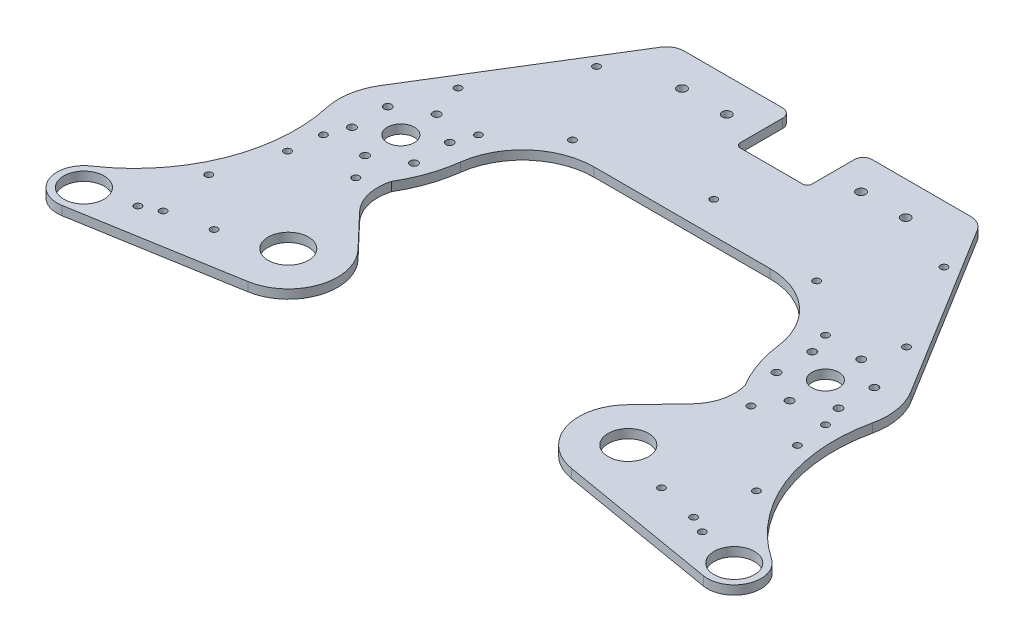
SolidWorks part; units mm, degrees
other "Marca1"
sketch "Croquis4" plane through (-508, 6.35, -221.5657) normal (0, 1, 0) x (1, 0, 0)
sketch "Croquis5" plane through (-262.5313, 6.35, -249.2375) normal (0, 1, 0) x (1, 0, 0)
sketch "Croquis6" plane through (-161.9393, 4.5, -121.1622) normal (0, 1, 0) x (1, 0, 0)
sketch "Croquis7" plane through (-262.5313, 6.35, -249.2375) normal (0, 1, 0) x (1, 0, 0)
sketch "Croquis9" plane through (-161.9393, 10.85, -121.1622) normal (0, 1, 0) x (1, 0, 0)
sketch "Croquis10" plane through (-262.5313, 6.35, -249.2375) normal (0, 1, 0) x (1, 0, 0)
sketch "Croquis12" plane through (-264.3199, 10.85, -20.8386) normal (0, 1, 0) x (1, 0, 0)
sketch "Croquis15" plane through (-262.5313, 6.35, -249.2375) normal (0, 1, 0) x (1, 0, 0)
sketch "Croquis16" plane through (-262.5313, 6.35, -249.2375) normal (0, 1, 0) x (1, 0, 0)
sketch "Croquis17" plane through (-262.5313, 6.35, -249.2375) normal (0, 1, 0) x (1, 0, 0)
sketch "Croquis18" plane through (-262.5313, 6.35, -249.2375) normal (0, 1, 0) x (1, 0, 0)
sketch "Croquis19" [suppressed] plane through (-264.3199, 10.85, -20.8386) normal (0, 1, 0) x (1, 0, 0)
sketch "Croquis20" [suppressed] plane through (-161.9393, 10.85, -121.1622) normal (0, 1, 0) x (1, 0, 0)
sketch "Croquis21" plane through (-264.3199, 10.85, -20.8386) normal (0, 1, 0) x (1, 0, 0)
sketch "Croquis22" plane through (-262.5313, 6.35, -249.2375) normal (0, 1, 0) x (1, 0, 0)
sketch "Croquis23" plane through (-262.5313, 6.35, -261.9375) normal (0, 1, 0) x (1, 0, 0)
sketch "Croquis24" plane through (-262.5313, 6.35, -261.9375) normal (0, 1, 0) x (1, 0, 0)
sketch "Croquis26" plane through (-262.5313, 7.9375, -34.9979) normal (0, 1, 0) x (1, 0, 0)
sketch "Croquis27" plane through (-262.5313, 6.35, -261.9375) normal (0, 1, 0) x (1, 0, 0)
sketch "Croquis28" plane through (-262.5313, 7.9375, -34.9979) normal (0, 1, 0) x (1, 0, 0)
sketch "Croquis29" plane through (-262.5313, 6.35, -261.9375) normal (0, 1, 0) x (1, 0, 0)
sketch "Croquis30" [suppressed] plane through (-262.5313, 7.9375, -34.9979) normal (0, 1, 0) x (1, 0, 0)
sketch "Croquis31" plane through (-262.5313, 7.9375, -34.9979) normal (0, 1, 0) x (1, 0, 0)
sketch "Croquis32" plane through (-161.9393, 10.85, -121.1622) normal (0, 1, 0) x (1, 0, 0)
sketch "Croquis33" plane through (-249.7931, 6.35, -261.9375) normal (0, 1, 0) x (1, 0, 0)
material "Acrílico (Impacto medio-alto)"
ref_plane "Alzado" through (0, 0, 0) normal (0, 0, 1) x (1, 0, 0)
ref_plane "Planta" through (0, 0, 0) normal (0, 1, 0) x (1, 0, 0)
ref_plane "Vista lateral" through (0, 0, 0) normal (1, 0, 0) x (0, 0, -1)
sketch "Dibujo" plane through (0, 0, 0) normal (0, 1, 0) x (1, 0, 0)
  line L0 (0, 0) -> (0, 158.75) construction
  line L1 (0, 158.75) -> (-508, 158.75) construction
  line L2 (-126.4251, 18.2045) -> (-236.5182, -16.7205) construction
  line L3 (-224.9681, -53.1295) -> (-114.8749, -18.2045) construction
  line L4 (-160.1534, 108.938) -> (-149.1603, -2.8048) construction
  line L5 (-141.9901, 113.8973) -> (-94.6704, 12.0732) construction
  circle A0 centre (-120.65, 0) radius 50.8
  circle A1 centre (-230.7431, -34.925) radius 28.575
  arc A2 (-236.5182, -16.7205) -> (-224.9681, -53.1295) centre (-230.7431, -34.925) ccw construction
  arc A3 (-114.8749, -18.2045) -> (-126.4251, 18.2045) centre (-120.65, 0) ccw construction
  circle A4 centre (-150.65, 109.8729) radius 30
  arc A5 (-141.9901, 113.8973) -> (-160.1534, 108.938) centre (-150.65, 109.8729) ccw construction
  arc A6 (-149.1603, -2.8048) -> (-94.6704, 12.0732) centre (-120.65, 0) ccw construction
  dimension "D1" = 101.6
  dimension "D5" = 57.15
  dimension "D6" = 38.1972
  dimension "D9" = 60
  dimension "D10" = 19.0986
  dimension "D11" = 57.2958
  dimension "D2" = 241.3
  dimension "D3" = 508
  dimension "D4" = 107.95
  dimension "D8" = 34.925
  dimension "D13" = 241.3
sketch "Croquis2" plane through (0, 0, 0) normal (0, 1, 0) x (1, 0, 0)
  line L0 (-227.5452, -53.7047) -> (-114.7749, -34.5012)
  line L1 (-188.1793, 133.0118) -> (-112.4104, 255.9027)
  line L2 (-101.6, 261.9375) -> (101.6, 261.9375)
  line L3 (0, 287.155) -> (0, -59.1328) construction
  line L4 (188.1793, 133.0118) -> (112.4104, 255.9027)
  line L5 (227.5452, -53.7047) -> (114.7749, -34.5012)
  line L6 (-95.3203, 24.1508) -> (-117.9194, 47.853)
  line L7 (-141.9901, 113.8973) -> (-94.6704, 12.0732) construction
  line L8 (0, 158.75) -> (-508, 158.75) construction
  line L9 (-62.4132, 158.75) -> (62.4132, 158.75)
  line L10 (95.3203, 24.1508) -> (117.9194, 47.853)
  line L12 (0, 158.75) -> (0, -117.475) construction
  line L13 (-117.475, -117.475) -> (117.475, -117.475) construction
  line L14 (-117.475, -117.475) -> (-117.475, 117.475) construction
  line L15 (-117.475, 117.475) -> (117.475, 117.475) construction
  line L16 (117.475, -117.475) -> (117.475, 117.475) construction
  line L17 (-117.475, -117.475) -> (117.475, 117.475) construction
  line L18 (-117.475, 117.475) -> (117.475, -117.475) construction
  line L20 (-25.4381, 261.9375) -> (25.4381, 261.9375)
  line L21 (-25.4381, 261.9375) -> (-25.4381, 222.25)
  line L22 (-25.4381, 222.25) -> (25.4381, 222.25)
  line L23 (25.4381, 261.9375) -> (25.4381, 222.25)
  line L24 (-25.4381, 261.9375) -> (25.4381, 222.25) construction
  line L25 (-25.4381, 222.25) -> (25.4381, 261.9375) construction
  circle A0 centre (-230.7431, -34.925) radius 14.3256
  circle A1 centre (-120.65, 0) radius 14.3256
  circle A3 centre (-230.7431, -34.925) radius 19.05
  circle A4 centre (-120.65, 0) radius 34.9979
  arc A6 (-149.1603, -2.8048) -> (-94.6704, 12.0732) centre (-120.65, 0) ccw construction
  arc A7 (-193.697, 100.3433) -> (-241.3934, -19.1303) centre (-305.2952, 75.6382) cw
  arc A8 (-112.4104, 255.9027) -> (-101.6, 261.9375) centre (-101.6, 249.2375) cw
  arc A10 (-117.9194, 47.853) -> (-125.3591, 78.1101) centre (-95.246, 69.4712) cw
  arc A11 (112.4104, 255.9027) -> (101.6, 261.9375) centre (101.6, 249.2375) ccw
  arc A12 (193.697, 100.3433) -> (241.3934, -19.1303) centre (305.2952, 75.6382) ccw
  arc A13 (-112.7986, 114.4272) -> (-62.4132, 158.75) centre (-62.4132, 107.95) cw
  arc A14 (188.1793, 133.0118) -> (193.697, 100.3433) centre (150.65, 109.8729) cw
  circle A15 centre (120.65, 0) radius 34.9979
  circle A16 centre (230.7431, -34.925) radius 19.05
  circle A17 centre (150.65, 109.8729) radius 9.5631
  circle A18 centre (120.65, 0) radius 14.3256
  circle A19 centre (230.7431, -34.925) radius 14.3256
  circle A20 centre (-150.65, 109.8729) radius 25.4 construction
  circle A21 centre (-150.65, 135.2729) radius 2.75
  circle A22 centre (-128.653, 122.5729) radius 2.75
  circle A23 centre (-128.653, 97.1729) radius 2.75
  circle A24 centre (-150.65, 84.4729) radius 2.75
  circle A25 centre (-172.647, 97.1729) radius 2.75
  circle A26 centre (-172.647, 122.5729) radius 2.75
  circle A27 centre (150.65, 109.8729) radius 25.4 construction
  circle A28 centre (172.647, 122.5729) radius 2.75
  circle A29 centre (172.647, 97.1729) radius 2.75
  circle A30 centre (150.65, 84.4729) radius 2.75
  circle A31 centre (128.653, 97.1729) radius 2.75
  circle A32 centre (128.653, 122.5729) radius 2.75
  circle A33 centre (150.65, 135.2729) radius 2.75
  arc A35 (-188.1793, 133.0118) -> (-193.697, 100.3433) centre (-150.65, 109.8729) ccw
  arc A36 (112.7986, 114.4272) -> (62.4132, 158.75) centre (62.4132, 107.95) ccw
  arc A37 (125.3591, 78.1101) -> (112.7986, 114.4272) centre (206.3577, 126.4546) cw
  circle A39 centre (-150.65, 109.8729) radius 9.5631
  circle A40 centre (-120.65, 0) radius 50.8 construction
  circle A41 centre (-150.65, 109.8729) radius 36.35 construction
  arc A42 (117.9194, 47.853) -> (125.3591, 78.1101) centre (95.246, 69.4712) ccw
  circle A43 centre (-150.65, 109.8729) radius 30 construction
  arc A44 (-125.3591, 78.1101) -> (-112.7986, 114.4272) centre (-206.3577, 126.4546) ccw
  point P53 (0, 261.9375)
  point P71 (-150.65, 109.8729)
  point P88 (-117.2099, 95.6223)
  point P89 (150.65, 109.8729)
  point P93 (0, 158.75)
  point P97 (0, 0)
  point P104 (0, 242.0938)
  dimension "D1" = 28.6512
  dimension "D2" = 6.35
  dimension "D3" = 6.35
  dimension "D4" = 38.1
  dimension "D5" = 114.3
  dimension "D6" = 31.3278
  dimension "D7" = 32.7493
  dimension "D9" = 12.7
  dimension "D11" = 50.8
  dimension "D12" = 5.5
  dimension "D10" = 50.8
  dimension "D14" = 234.95
  dimension "D15" = 94.329
  dimension "D16" = 6.2059
  dimension "D17" = 34.4369
  dimension "D21" = 19.1262
  dimension "D8" = 203.2
  dimension "D18" = 50.8762
  dimension "D19" = 39.6875
  dimension "D20" = 63.5
  dimension "D13" = 6
extrude "Saliente-Extruir1" add sketch "Croquis2" along normal blind 6.35 contours A15 L5 A16 A12 A14 L4 A11 L2 A8 L1 A35 A7 A3 L0 A4 A32 A30 A28 A26 A25 A24 A23 A22 A21 A39 A17 A29 A31 A33 | A15 A18 | A16 A19 | A4 A1 | A3 A0 | L23 L2 L21 L22 | A39 | A25 | A26 | A22 | A23 | A24 | A21 | A17 | A33 | A32 | A28 | A31 | A30 | A29 region at (-211.7782, 0, 50.9334) region at (-247.9271, 0, 41.8078) region at (-152.9287, 0, -10.7066) region at (0, 0, -242.0938) region at (133.2892, 0, -31.5721) region at (247.0869, 0, 26.2333) region at (150.65, 0, -109.8729) region at (-150.65, 0, -135.2729) region at (-128.653, 0, -122.5729) region at (-128.653, 0, -97.1729) region at (-150.65, 0, -84.4729) region at (-172.647, 0, -97.1729) region at (-172.647, 0, -122.5729) region at (172.647, 0, -122.5729) region at (172.647, 0, -97.1729) region at (150.65, 0, -84.4729) region at (128.653, 0, -97.1729) region at (128.653, 0, -122.5729) region at (150.65, 0, -135.2729) region at (-150.65, 0, -109.8729)
extrude "Cortar-Extruir1" cut sketch "Croquis2<4>" along normal through all contours L23 L2 L21 L22 | A17 | A29 | A30 | A31 | A32 | A33 | A28 | A39 | A26 | A21 | A22 | A23 | A25 | A24 region at (0, 0, -242.0938) region at (150.65, 0, -109.8729) region at (-150.65, 0, -135.2729) region at (-128.653, 0, -122.5729) region at (-128.653, 0, -97.1729) region at (-150.65, 0, -84.4729) region at (-172.647, 0, -97.1729) region at (-172.647, 0, -122.5729) region at (172.647, 0, -122.5729) region at (172.647, 0, -97.1729) region at (150.65, 0, -84.4729) region at (128.653, 0, -97.1729) region at (128.653, 0, -122.5729) region at (150.65, 0, -135.2729) region at (-150.65, 0, -109.8729)
sketch "Croquis2<4>" plane through (0, 0, 0) normal (0, 1, 0) x (1, 0, 0) same geometry as "Croquis2"
sketch "Croquis14" plane through (0, 6.35, 0) normal (0, 1, 0) x (1, 0, 0)
  line L0 (-227.5452, -53.7047) -> (-114.7749, -34.5012) construction
  line L1 (-101.6, 261.9375) -> (-25.4381, 261.9375) construction
  line L2 (-25.4381, 261.9375) -> (-25.4381, 222.25) construction
  line L3 (-150.65, 109.8729) -> (-178.1494, 82.3735) construction
  line L4 (-150.65, 109.8729) -> (-150.65, 78.9066) construction
  line L5 (0, 158.75) -> (-508, 158.75) construction
  line L6 (-184.0813, 84.6396) -> (-171.4116, 117.8043)
  line L7 (-188.1793, 133.0118) -> (-112.4104, 255.9027) construction
  line L8 (-175.8833, 76.4416) -> (-142.7186, 89.1113)
  line L9 (-62.4132, 158.75) -> (62.4132, 158.75) construction
  line L10 (-150.65, 109.8729) -> (-164.4835, 123.7064) construction
  line L11 (25.4381, 261.9375) -> (25.4381, 222.25) construction
  line L12 (0, 0) -> (0, 222.25) construction
  line L13 (-25.4381, 222.25) -> (25.4381, 222.25) construction
  line L14 (-117.2187, 135.1062) -> (-129.8884, 101.9415)
  line L15 (-125.4167, 143.3042) -> (-158.5814, 130.6345)
  line L16 (0, 263.811) -> (0, 117.8043) construction
  line L17 (-135.7241, 31.5852) -> (-238.9692, -17.6887) construction
  circle A0 centre (-188.1981, -21.2387) radius 4.7625
  circle A1 centre (-188.1981, -21.2387) radius 2.4892
  circle A2 centre (-230.7431, -34.925) radius 28.575 construction
  circle A5 centre (-194.31, 17.2379) radius 4.7625
  circle A6 centre (-194.31, 17.2379) radius 2.4892
  circle A7 centre (-180.9008, 59.69) radius 4.7625
  circle A8 centre (-180.9008, 59.69) radius 2.4892
  arc A9 (-241.3934, -19.1303) -> (-193.697, 100.3433) centre (-305.2952, 75.6382) ccw construction
  circle A10 centre (-47.625, 238.125) radius 4.7625
  circle A11 centre (-47.625, 238.125) radius 3.2639
  circle A12 centre (-79.375, 238.125) radius 4.7625
  circle A13 centre (-79.375, 238.125) radius 3.2639
  circle A14 centre (-120.65, 0) radius 50.8 construction
  circle A15 centre (-140.2263, 67.4904) radius 4.7625
  circle A16 centre (-140.2263, 67.4904) radius 2.4892
  circle A17 centre (47.625, 238.125) radius 3.2639
  circle A18 centre (47.625, 238.125) radius 4.7625
  arc A19 (-125.3591, 78.1101) -> (-117.9194, 47.853) centre (-95.246, 69.4712) ccw construction
  circle A20 centre (79.375, 238.125) radius 3.2639
  circle A21 centre (-150.65, 109.8729) radius 30 construction
  circle A22 centre (0, 181.2925) radius 4.7625
  circle A23 centre (0, 181.2925) radius 2.4892
  circle A24 centre (-86.6348, 167.64) radius 4.7625
  circle A25 centre (-86.6348, 167.64) radius 2.4892
  circle A26 centre (-159.1395, 158.938) radius 4.7625
  circle A27 centre (-159.1395, 158.938) radius 2.4892
  circle A28 centre (188.1981, -21.2387) radius 2.4892
  circle A29 centre (188.1981, -21.2387) radius 4.7625
  circle A30 centre (194.31, 17.2379) radius 2.4892
  circle A31 centre (194.31, 17.2379) radius 4.7625
  circle A32 centre (180.9008, 59.69) radius 2.4892
  circle A33 centre (180.9008, 59.69) radius 4.7625
  circle A34 centre (140.2263, 67.4904) radius 2.4892
  circle A35 centre (140.2263, 67.4904) radius 4.7625
  circle A36 centre (86.6348, 167.64) radius 2.4892
  circle A37 centre (86.6348, 167.64) radius 4.7625
  circle A38 centre (159.1395, 158.938) radius 2.4892
  circle A39 centre (159.1395, 158.938) radius 4.7625
  circle A40 centre (79.375, 238.125) radius 4.7625
  circle A41 centre (-178.1494, 82.3735) radius 6.35
  circle A42 centre (-178.1494, 82.3735) radius 2.4892
  circle A45 centre (-150.65, 109.8729) radius 30 construction
  circle A46 centre (-150.65, 109.8729) radius 22.225
  circle A47 centre (-123.1506, 137.3723) radius 2.4892
  circle A48 centre (-123.1506, 137.3723) radius 6.35
  circle A49 centre (-123.2693, 221.3514) radius 4.7625
  circle A50 centre (-123.2693, 221.3514) radius 2.4892
  circle A51 centre (178.1494, 82.3735) radius 6.35
  circle A52 centre (178.1494, 82.3735) radius 2.4892
  circle A53 centre (123.1506, 137.3723) radius 6.35
  circle A54 centre (123.1506, 137.3723) radius 2.4892
  circle A55 centre (123.2693, 221.3514) radius 2.4892
  circle A56 centre (123.2693, 221.3514) radius 4.7625
  circle A57 centre (-200.2631, -27.1581) radius 4.7625
  circle A58 centre (-200.2631, -27.1581) radius 2.4892
  circle A59 centre (-158.75, -14.5845) radius 4.7625
  circle A60 centre (-158.75, -14.5845) radius 2.4892
  circle A61 centre (-120.65, 0) radius 14.3256 construction
  circle A62 centre (-120.65, 0) radius 34.9979 construction
  arc A63 (-114.7749, -34.5012) -> (-95.3203, 24.1508) centre (-120.65, 0) ccw construction
  arc A64 (-236.5182, -16.7205) -> (-224.9681, -53.1295) centre (-230.7431, -34.925) ccw construction
  circle A65 centre (-230.7431, -34.925) radius 14.3256 construction
  circle A66 centre (158.75, -14.5845) radius 4.7625
  circle A67 centre (158.75, -14.5845) radius 2.4892
  circle A68 centre (200.2631, -27.1581) radius 4.7625
  circle A69 centre (200.2631, -27.1581) radius 2.4892
  dimension "D1" = 9.525
  dimension "D2" = 4.9784
  dimension "D3" = 25.4
  dimension "D4" = 42.545
  dimension "D5" = 6.35
  dimension "D6" = 6.35
  dimension "D7" = 8.89
  dimension "D8" = 73.66
  dimension "D9" = 8.89
  dimension "D10" = 7.62
  dimension "D11" = 8.89
  dimension "D12" = 63.5
  dimension "D13" = 17.78
  dimension "D14" = 20.6756
  dimension "D15" = 63.5
  dimension "D16" = 6.35
  dimension "D17" = 23.8125
  dimension "D18" = 22.1869
  dimension "D19" = 31.75
  dimension "D20" = 45
  dimension "D21" = 12.7
  dimension "D22" = 60
  dimension "D23" = 2.54
  dimension "D24" = 44.45
  dimension "D26" = 6.5278
  dimension "D27" = 8.89
  dimension "D28" = 46.99
  dimension "D29" = 38.1
  dimension "D30" = 31.75
  dimension "D31" = 30.48
  dimension "D32" = 21.59
  dimension "D25" = 90
extrude "Cortar-Extruir2" cut sketch "Croquis14" against normal through all contours A1 | A6 | A8 | A16 | A27 | A25 | A23 L12 | L12 A23 | A36 | A38 | A34 | A32 | A30 | A28 | A13 | A11 | A17 | A20 | A55 | A54 | A52 | A47 | A50 | A42 | A60 | A58 | A67 | A69 region at (-188.1981, 6.35, 21.2387) region at (-194.31, 6.35, -17.2379) region at (-180.9008, 6.35, -59.69) region at (-47.625, 6.35, -238.125) region at (-79.375, 6.35, -238.125) region at (-140.2263, 6.35, -67.4904) region at (47.625, 6.35, -238.125) region at (79.375, 6.35, -238.125) region at (0, 6.35, -181.2925) region at (-86.6348, 6.35, -167.64) region at (-159.1395, 6.35, -158.938) region at (188.1981, 6.35, 21.2387) region at (194.31, 6.35, -17.2379) region at (180.9008, 6.35, -59.69) region at (140.2263, 6.35, -67.4904) region at (86.6348, 6.35, -167.64) region at (159.1395, 6.35, -158.938) region at (-178.1494, 6.35, -82.3735) region at (-123.1506, 6.35, -137.3723) region at (-123.2693, 6.35, -221.3514) region at (178.1494, 6.35, -82.3735) region at (123.1506, 6.35, -137.3723) region at (123.2693, 6.35, -221.3514) region at (-200.2631, 6.35, 27.1581) region at (-158.75, 6.35, 14.5845) region at (158.75, 6.35, 14.5845) region at (200.2631, 6.35, 27.1581)
fillet "Redondeo1" radius 6.35 2 edges at (25.4381, 3.175, -261.9375) (-25.4381, 3.175, -261.9375)
fillet "Redondeo2" radius 3.175 2 edges at (-25.4381, 3.175, -222.25) (25.4381, 3.175, -222.25)
sketch "Croquis8" [suppressed] plane through (0, 6.35, 0) normal (0, 1, 0) x (1, 0, 0)
  line L0 (-141.9901, 113.8973) -> (-94.6704, 12.0732) construction
  line L1 (-160.1534, 108.938) -> (-149.1603, -2.8048) construction
  line L2 (-141.9901, 113.8973) -> (-94.6704, 12.0732) construction
  line L3 (-160.1534, 108.938) -> (-149.1603, -2.8048) construction
  line L4 (-158.1033, 109.1397) -> (-147.1102, -2.6031)
  line L5 (-143.8583, 113.0292) -> (-96.5386, 11.2051)
  line L6 (-161.8851, 108.7676) -> (-150.8919, -2.9752)
  line L7 (-140.4122, 114.6306) -> (-93.0925, 12.8065)
  arc A0 (-141.9901, 113.8973) -> (-160.1534, 108.938) centre (-150.65, 109.8729) ccw construction
  arc A1 (-149.1603, -2.8048) -> (-94.6704, 12.0732) centre (-120.65, 0) ccw construction
  arc A2 (-141.9901, 113.8973) -> (-160.1534, 108.938) centre (-150.65, 109.8729) ccw construction
  arc A3 (-149.1603, -2.8048) -> (-94.6704, 12.0732) centre (-120.65, 0) ccw construction
  arc A4 (-147.1102, -2.6031) -> (-96.5386, 11.2051) centre (-120.65, 0) ccw
  arc A5 (-143.8583, 113.0292) -> (-158.1033, 109.1397) centre (-150.65, 109.8729) ccw
  arc A6 (-150.8919, -2.9752) -> (-93.0925, 12.8065) centre (-120.65, 0) ccw
  arc A7 (-140.4122, 114.6306) -> (-161.8851, 108.7676) centre (-150.65, 109.8729) ccw
  dimension "D1" = 2.06
  dimension "D2" = 3.8
extrude "Saliente-Extruir2" [suppressed] add sketch "Croquis8" along normal mid plane 9 separate body
delete or keep bodies "Sólido-Eliminar/Conservar 1" [suppressed] type delete bodies bodies 106
sketch "Croquis11" [suppressed] plane through (0, 6.35, 0) normal (0, 1, 0) x (1, 0, 0)
  line L0 (-238.258, -53.2954) -> (-115.4267, -18.3704) construction
  line L1 (-125.8733, 18.3704) -> (-248.7046, -16.5546) construction
  line L2 (-238.258, -53.2954) -> (-115.4267, -18.3704) construction
  line L3 (-125.8733, 18.3704) -> (-248.7046, -16.5546) construction
  line L4 (-125.3099, 16.389) -> (-248.1413, -18.536)
  line L5 (-238.8214, -51.314) -> (-115.9901, -16.389)
  line L6 (-126.3492, 20.0441) -> (-249.1805, -14.8809)
  line L7 (-237.7821, -54.9691) -> (-114.9508, -20.0441)
  arc A0 (-115.4267, -18.3704) -> (-125.8733, 18.3704) centre (-120.65, 0) ccw construction
  arc A1 (-248.7046, -16.5546) -> (-238.258, -53.2954) centre (-243.4813, -34.925) ccw construction
  arc A2 (-115.4267, -18.3704) -> (-125.8733, 18.3704) centre (-120.65, 0) ccw construction
  arc A3 (-248.7046, -16.5546) -> (-238.258, -53.2954) centre (-243.4813, -34.925) ccw construction
  arc A4 (-248.1413, -18.536) -> (-238.8214, -51.314) centre (-243.4813, -34.925) ccw
  arc A5 (-115.9901, -16.389) -> (-125.3099, 16.389) centre (-120.65, 0) ccw
  arc A6 (-249.1805, -14.8809) -> (-237.7821, -54.9691) centre (-243.4813, -34.925) ccw
  arc A7 (-114.9508, -20.0441) -> (-126.3492, 20.0441) centre (-120.65, 0) ccw
  dimension "D1" = 2.06
  dimension "D2" = 3.8
extrude "Saliente-Extruir3" [suppressed] add sketch "Croquis11" along normal mid plane 9 separate body
delete or keep bodies "Sólido-Eliminar/Conservar 2" [suppressed] type delete bodies bodies 106
sketch "Croquis25" [suppressed] plane through (0, 6.35, 0) normal (0, 1, 0) x (1, 0, 0)
  line L0 (-115.3574, -34.5954) -> (-240.6004, -53.7559)
  line L1 (-134.3508, 32.2047) -> (-250.9389, -17.3954)
  arc A0 (-115.3574, -34.5954) -> (-134.3508, 32.2047) centre (-120.65, 0) ccw
  arc A1 (-250.9389, -17.3954) -> (-240.6004, -53.7559) centre (-243.4813, -34.925) ccw
  arc A2 (-251.6976, -17.7379) -> (-240.6004, -53.7559) centre (-243.4813, -34.925) ccw construction
  arc A3 (-115.3574, -34.5954) -> (-95.3203, 24.1508) centre (-120.65, 0) ccw construction
  circle A4 centre (-158.75, -12.6793) radius 4.7625
  circle A5 centre (-158.75, -12.6793) radius 2.4892
  circle A8 centre (-120.65, 0) radius 14.3256 construction
  circle A9 centre (-213.0013, -27.6924) radius 4.7625
  circle A10 centre (-213.0013, -27.6924) radius 2.4892
  circle A11 centre (-243.4813, -34.925) radius 14.3256 construction
  circle A12 centre (-120.65, 0) radius 14.3256
  circle A13 centre (-243.4813, -34.925) radius 14.3256
  dimension "D1" = 4.9784
  dimension "D2" = 9.525
  dimension "D3" = 38.1
  dimension "D4" = 31.75
  dimension "D5" = 30.48
  dimension "D6" = 21.59
extrude "Saliente-Extruir4" [suppressed] add sketch "Croquis25" along normal blind 1.5875 separate body contours L1 A1 L0 A0 A13 A12 A9 A4 | A9 A10 | A4 A5
delete or keep bodies "Sólido-Eliminar/Conservar 3" [suppressed] type keep bodies bodies 112
equation "\"D7@Dibujo\"=( 70 * 5mm )  + 1mm"
equation "\"D10@Dibujo\" = 12 * 5mm / pi"
equation "\"D11@Dibujo\" = 36 * 5mm / pi"
equation "\"D12@Dibujo\" =  ( 70 * 5mm )  + 1mm"
